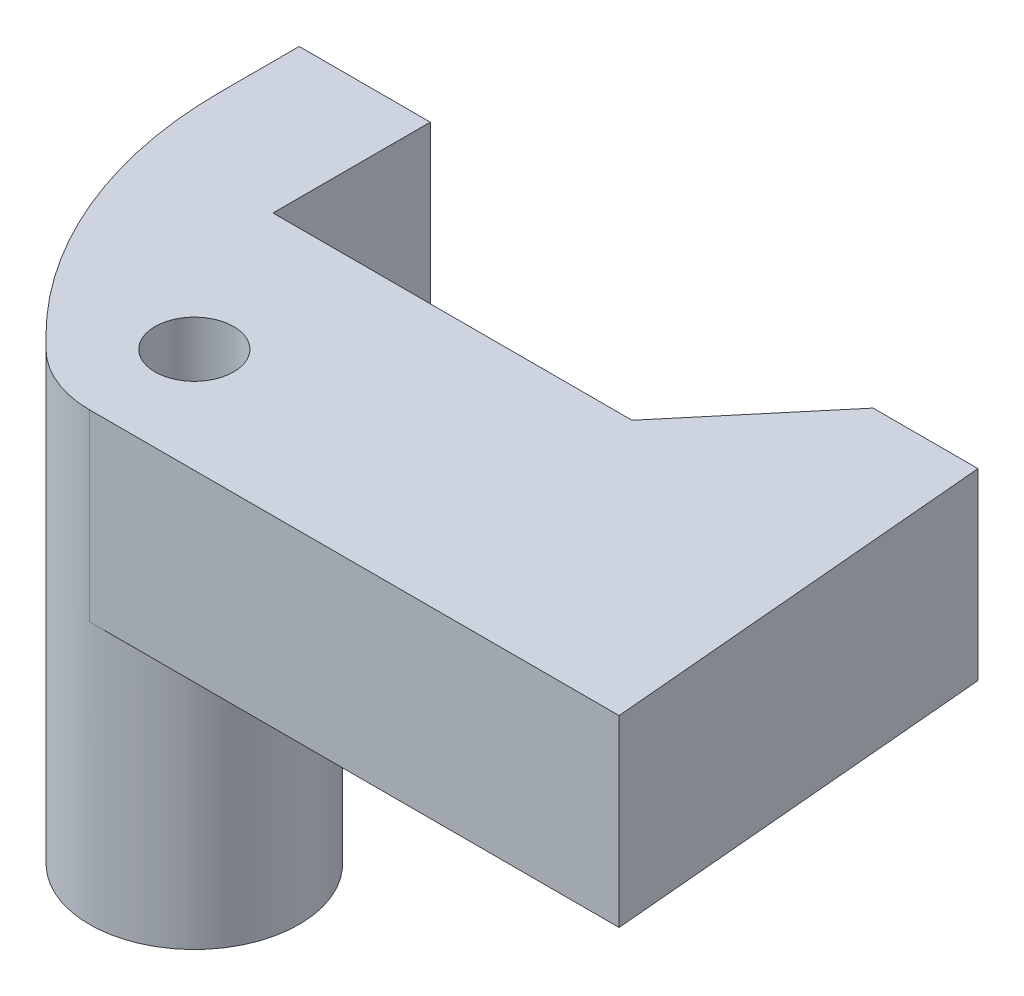
SolidWorks part; units mm, degrees
ref_plane "Front Plane" through (0, 0, 0) normal (0, 0, 1) x (1, 0, 0)
ref_plane "Top Plane" through (0, 0, 0) normal (0, 1, 0) x (1, 0, 0)
ref_plane "Right Plane" through (0, 0, 0) normal (1, 0, 0) x (0, 0, -1)
sketch "Sketch1" plane through (0, 0, 0) normal (0, 1, 0) x (1, 0, 0)
  line L0 (0, 32.3882) -> (0, 7) construction
  line L1 (0, 7) -> (6, 7) construction
  line L2 (6, 7) -> (39, 22.3882) construction
  line L3 (39, 22.3882) -> (72, 7) construction
  line L4 (72, 7) -> (78, 7) construction
  line L5 (78, 7) -> (78, 32.3882) construction
  line L6 (78, 32.3882) -> (0, 32.3882) construction
  line L7 (-11, 13) -> (-11, 16)
  line L8 (11.8877, 15) -> (15.8877, 15)
  line L9 (-3, 0) -> (17.2, 0)
  line L10 (17.5, 15.9916) -> (17.5, 0.8497) construction
  line L11 (17.2, 0) -> (15.8877, 15)
  line L12 (11.8877, 15) -> (7.6922, 10)
  line L13 (7.6922, 10) -> (-6, 10)
  line L14 (-11, 16) -> (-6, 16)
  line L15 (-6, 16) -> (-6, 10)
  line L16 (-5.8284, 1.1716) -> (-6.2929, 1.636)
  line L19 (-3, 4) -> (-3, 0) construction
  circle A0 centre (-3, 4) radius 1.5
  circle A1 centre (-3, 4) radius 4 construction
  circle A2 centre (39, -0.5) radius 21 construction
  circle A3 centre (18.4662, -10) radius 21 construction
  arc A4 (-11, 13) -> (-6.2929, 1.636) centre (5.0711, 13) ccw
  arc A5 (-3, 0) -> (-5.8284, 1.1716) centre (-3, 4) cw
  dimension "D5" = 3
  dimension "D11" = 3
  dimension "D13" = 42
  dimension "D3" = 130
  dimension "D23" = 4
  dimension "D24" = 8
  dimension "D1" = 6
  dimension "D2" = 78
  dimension "D4" = 10
  dimension "D6" = 7
  dimension "D7" = 3
  dimension "D8" = 85
  dimension "D9" = 20.2
  dimension "D10" = 17.5
  dimension "D12" = 15
  dimension "D14" = 4
  dimension "D15" = 3
  dimension "D16" = 50
  dimension "D17" = 4
  dimension "D18" = 10
  dimension "D19" = 0.5
  dimension "D20" = 6
  dimension "D21" = 5
  dimension "D25" = 10
  dimension "D26" = 135
extrude "Boss-Extrude1" add sketch "Sketch1" along normal blind 7
sketch "Sketch2" plane through (0, 0, 0) normal (0, -1, 0) x (1, 0, 0)
  line L0 (-5.8284, -1.1716) -> (-6.2929, -1.636)
  line L3 (-11, -13) -> (-11, -16)
  line L4 (-11, -16) -> (-6, -16)
  line L5 (-6, -16) -> (-6, -8)
  line L6 (-6, -8) -> (-3, -8)
  line L7 (-11, -16) -> (-11, -13) construction
  arc A0 (-3, 0) -> (-3, -8) centre (-3, -4) cw
  circle A1 centre (-3, -4) radius 1.5
  arc A2 (-3, 0) -> (-5.8284, -1.1716) centre (-3, -4) ccw
  arc A3 (-6.2929, -1.636) -> (-11, -13) centre (5.0711, -13) ccw construction
  arc A4 (-6.2929, -1.636) -> (-11, -13) centre (5.0711, -13) ccw
  dimension "D2" = 3
extrude "Boss-Extrude2" add sketch "Sketch2" along normal blind 10
